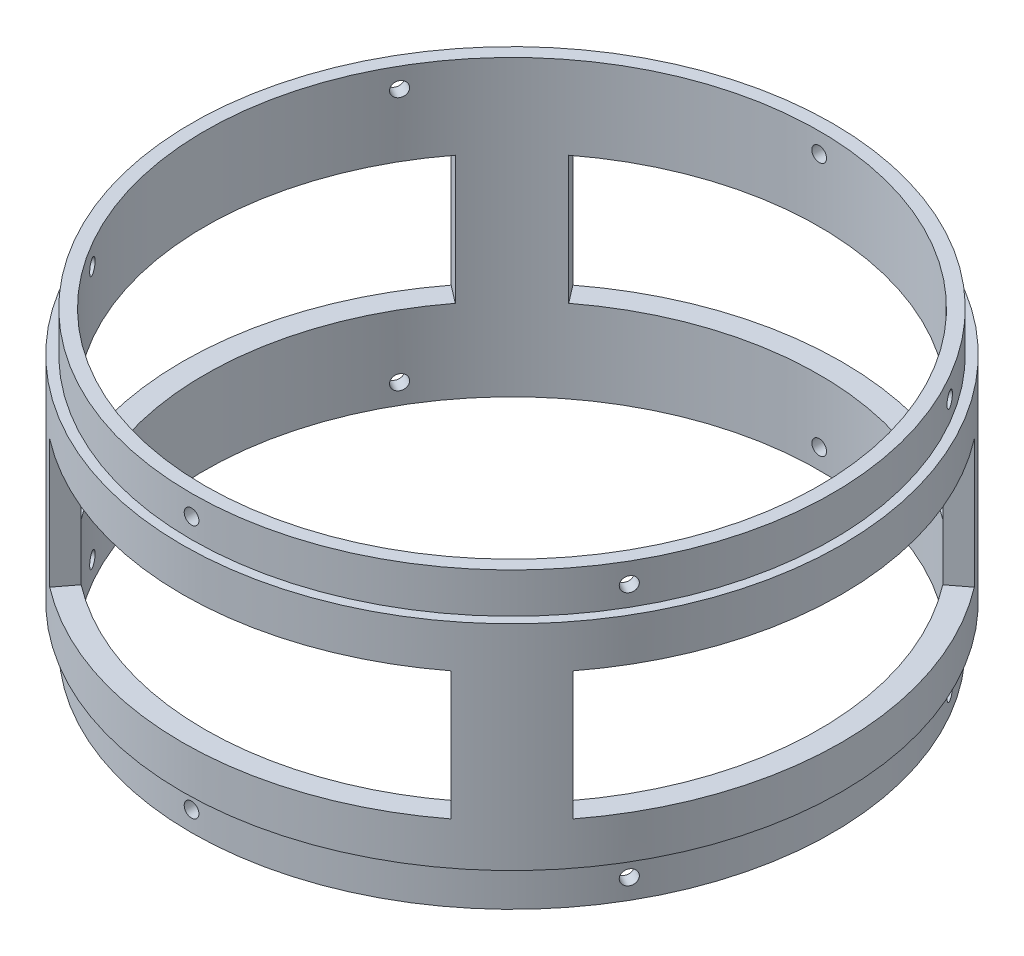
SolidWorks part; units mm, degrees
ref_plane "Front Plane" through (0, 0, 0) normal (0, 0, 1) x (1, 0, 0)
ref_plane "Top Plane" through (0, 0, 0) normal (0, 1, 0) x (1, 0, 0)
ref_plane "Right Plane" through (0, 0, 0) normal (1, 0, 0) x (0, 0, -1)
sketch "Sketch1" plane through (0, 0, 0) normal (0, 1, 0) x (1, 0, 0)
  line L0 (0, 0) -> (-47.7019, 62.1664)
  line L1 (0, 0) -> (47.7019, 62.1664)
  line L2 (0, 0) -> (0, 72.1431) construction
  circle A0 centre (0, 0) radius 78.359
  circle A1 centre (0, 0) radius 73.025
  circle A2 centre (0, 0) radius 76.1746
  dimension "D1" = 156.718
  dimension "D2" = 146.05
  dimension "D3" = 152.3492
  dimension "D4" = 75
extrude "Boss-Extrude1" add sketch "Sketch1" along normal blind 50.8 contours L2 A2 L1 A0 | L2 A1 L1 A2 | L2 A2 L1 A1 | L2 A0 L1 A2 | A2 L2 A1 L0 | A0 L2 A2 L0 | A2 L2 A0 L0 | A1 L2 A2 L0 region at (-33.2032, 0, 67.3294) region at (-44.6636, 0, -59.7594) region at (-34.6222, 0, 70.2068) region at (-46.2669, 0, -61.8908)
ref_plane "Plane1" through (0, 25.4, 0) normal (0, 1, 0) x (1, 0, 0)
extrude "Boss-Extrude2" add sketch "Sketch1<3>" along normal blind 9.525 from surface contours A2 L2 A1 L0 | L2 A2 L1 A1 | L2 A1 L1 A2 | A1 L2 A2 L0 region at (-33.2032, 0, 67.3294) region at (-44.6636, 0, -59.7594) starting at face at (0, 50.8, 73.025)
sketch "Sketch1<3>" plane through (0, 0, 0) normal (0, 1, 0) x (1, 0, 0) same geometry as "Sketch1"
extrude "Boss-Extrude3" add sketch "Sketch1<4>" against normal blind 9.525 contours A2 L2 A1 L0 | A1 L2 A2 L0 | L2 A1 L1 A2 | L2 A2 L1 A1 region at (-33.2032, 0, 67.3294) region at (-44.6636, 0, -59.7594)
sketch "Sketch1<4>" plane through (0, 0, 0) normal (0, 1, 0) x (1, 0, 0) same geometry as "Sketch1"
ref_plane "Plane2" through (0, 0, -76.1746) normal (0, 0, -1) x (-1, 0, 0)
ref_axis "Axis1" through (0, 0, 0) along (0, 1, 0)
sketch "Sketch3" plane through (0, 0, -76.1746) normal (0, 0, -1) x (-1, 0, 0)
  line L0 (76.1746, 0) -> (-76.1746, 0) construction
  line L1 (-76.1746, -9.525) -> (76.1746, -9.525) construction
  line L2 (76.1746, 50.8) -> (-76.1746, 50.8) construction
  line L3 (76.1746, 60.325) -> (-76.1746, 60.325) construction
  line L4 (76.1746, 0) -> (-76.1746, 0)
  line L5 (-76.1746, -9.525) -> (76.1746, -9.525)
  line L6 (76.1746, 50.8) -> (-76.1746, 50.8)
  line L7 (76.1746, 60.325) -> (-76.1746, 60.325)
  line L8 (0, 60.325) -> (0, 50.8)
  line L9 (0, 0) -> (0, -9.525)
  circle A0 centre (0, 55.5625) radius 1.75
  circle A1 centre (0, -4.7625) radius 1.75
  point P12 (0, 55.5625)
  point P13 (0, -4.7625)
  point P14 (-77.5445, 179.1871)
  dimension "D1" = 3.5
extrude "Cut-Extrude2" cut sketch "Sketch3" against normal up to next contours L8 A0 | L8 A0 | L9 A1 | L9 A1 region at (-0.7427, 55.5625, -76.1746) region at (0.7427, 55.5625, -76.1746) region at (-0.7427, -4.7625, -76.1746) region at (0.7427, -4.7625, -76.1746)
extrude "Cut-Extrude3" cut sketch "Sketch1<7>" against normal blind 15.24 and the other way blind 15.24 from surface contours L2 A1 L1 A2 | A1 L2 A2 L0 | A2 L2 A0 L0 | L2 A2 L1 A0 region at (-44.6636, 0, -59.7594) region at (-46.2669, 0, -61.8908) starting at plane "Plane1"
sketch "Sketch1<7>" plane through (0, 0, 0) normal (0, 1, 0) x (1, 0, 0) same geometry as "Sketch1"
pattern_circular "CirPattern2" count 4 over 360 about axis through (0, 0, 0) along (0, 1, 0) of "Cut-Extrude3"
pattern_circular "CirPattern3" count 6 over 360 about axis through (0, 0, 0) along (0, 1, 0) of "Cut-Extrude2"
equation "\"AB_Coupler_OD_Length\"= 2in"
equation "\"AB_Coupling_Section_Length\"= 0.375in"
equation "\"AB_Coupler_Length\"= \"AB_Coupler_OD_Length\" + \"AB_Coupling_Section_Length\" * 2"
equation "\"D1@Boss-Extrude2\"=\"AB_Coupling_Section_Length\""
equation "\"D1@Boss-Extrude3\"=\"AB_Coupling_Section_Length\""
equation "\"D1@Boss-Extrude1\" = \"AB_Coupler_OD_Length\""
equation "\"Cutout_Angle\" = 75"
equation "\"AB_Coupler_Num_Screws\"= 6"
equation "\"Num_Cutouts\" = 4"
equation "\"D4@Sketch1\"=\"Cutout_Angle\""
equation "\"D1@CirPattern2\"=\"Num_Cutouts\""
equation "\"D1@CirPattern3\"=\"AB_Coupler_Num_Screws\""
equation "\"AB_Coupler_OD\"= 6.17in"
equation "\"AB_Coupler_ID\"= 5.75in"
equation "\"AB_Coupler_Surface_Diameter\"= 5.998in"
equation "\"D3@Sketch1\"=\"AB_Coupler_Surface_Diameter\""
equation "\"D2@Sketch1\"=\"AB_Coupler_ID\""
equation "\"D1@Sketch1\"=\"AB_Coupler_OD\""
equation "\"AB_Coupling_Screw_Diameter\"= 3.5mm"
equation "\"Aft_Section_Length\"= 40in"
equation "\"Aft_Lower_Length\"= 20in"
equation "\"Aft_Upper_Length\"= \"Aft_Section_Length\" - \"Aft_Lower_Length\" - \"AB_Coupler_OD_Length\""
